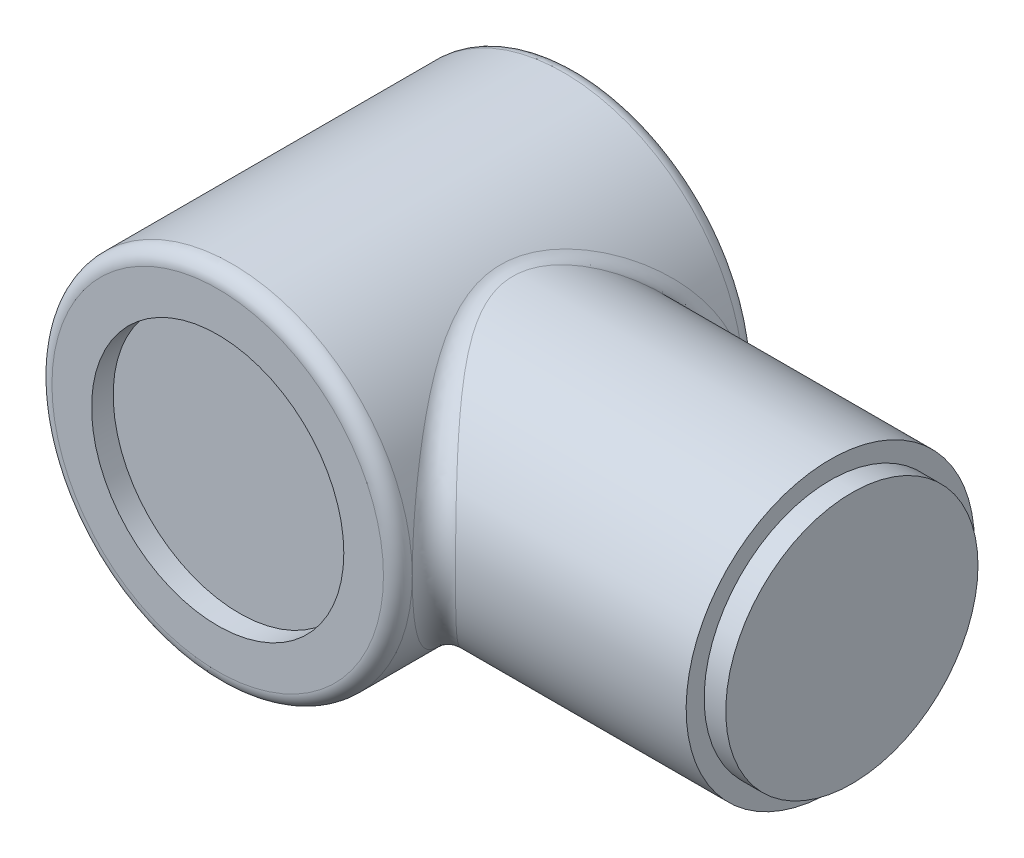
SolidWorks part; units mm, degrees
ref_plane "Front Plane" through (0, 0, 0) normal (0, 0, 1) x (1, 0, 0)
ref_plane "Top Plane" through (0, 0, 0) normal (0, 1, 0) x (1, 0, 0)
ref_plane "Right Plane" through (0, 0, 0) normal (1, 0, 0) x (0, 0, -1)
sketch "Sketch1" plane through (0, 0, 0) normal (0, 0, 1) x (1, 0, 0)
  circle A0 centre (0, 0) radius 25
  dimension "D1" = 50
extrude "Boss-Extrude1" add sketch "Sketch1" along normal blind 50
sketch "Sketch2" plane through (0, 0, 50) normal (0, 0, 1) x (1, 0, 0)
  circle A0 centre (0, 0) radius 17.5
  dimension "D1" = 35
extrude "Cut-Extrude1" cut sketch "Sketch2" against normal blind 3
sketch "Sketch3" plane through (0, 0, 0) normal (0, 0, -1) x (-1, 0, 0)
  circle A0 centre (0, 0) radius 17.5
  dimension "D1" = 35
extrude "Cut-Extrude2" cut sketch "Sketch3" against normal blind 3
sketch "Sketch4" plane through (0, 0, 0) normal (1, 0, 0) x (0, 0, -1)
  circle A0 centre (-25, 0) radius 20
  dimension "D1" = 40
extrude "Boss-Extrude2" add sketch "Sketch4" along normal blind 60
sketch "Sketch5" plane through (60, 0, 0) normal (1, 0, 0) x (0, 0, -1)
  circle A3 centre (-25, 0) radius 17.5
  dimension "D1" = 35
extrude "Boss-Extrude3" add sketch "Sketch5" along normal blind 3
fillet "Fillet1" radius 3 1 edges at (24.89, 2.3429, 5.1377)
fillet "Fillet2" radius 2 2 edges at (25, 0, 0) (25, 0, 50)
